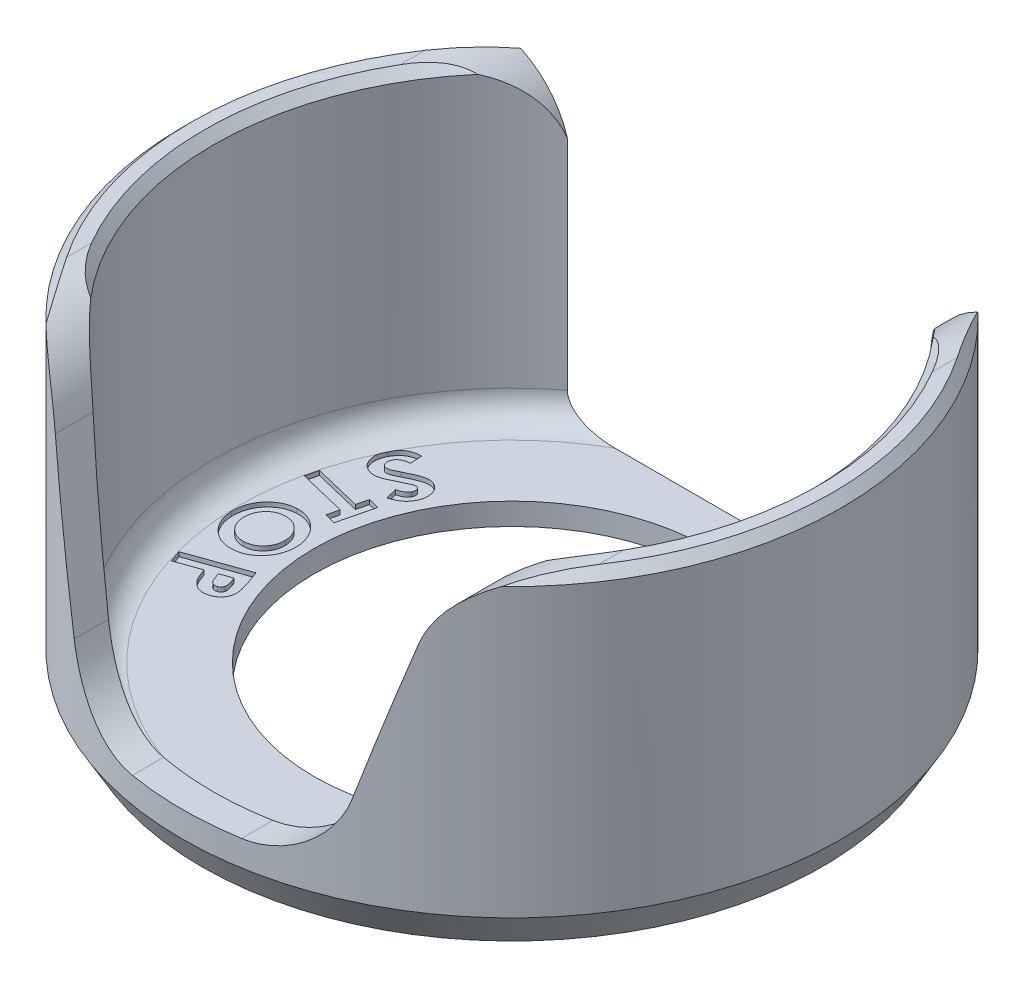
SolidWorks part; units mm, degrees
ref_plane "Front Plane" through (0, 0, 0) normal (0, 0, 1) x (1, 0, 0)
ref_plane "Top Plane" through (0, 0, 0) normal (0, 1, 0) x (1, 0, 0)
ref_plane "Right Plane" through (0, 0, 0) normal (1, 0, 0) x (0, 0, -1)
sketch "Sketch1" plane through (0, 0, 0) normal (0, 1, 0) x (1, 0, 0)
  circle A0 centre (0, 0) radius 37.5
  circle A1 centre (0, 0) radius 22.5
  dimension "D1" = 75
  dimension "D2" = 45
extrude "Boss-Extrude1" add sketch "Sketch1" along normal blind 2.5
sketch "Sketch2" plane through (0, 2.5, 0) normal (0, 1, 0) x (1, 0, 0)
  circle A0 centre (0, 0) radius 34
  circle A1 centre (0, 0) radius 37.5
extrude "Boss-Extrude2" add sketch "Sketch2" along normal blind 35
fillet "Fillet1" radius 3 1 edges at (0, 2.5, 34)
chamfer "Chamfer1" distance 1 angle 45 2 edges at (0, 37.5, 37.5) (0, 37.5, 34)
sketch "Sketch3" plane through (0, 0, 0) normal (0, 0, 1) x (1, 0, 0)
  line L8 (35, 37.5) -> (-35, 37.5) construction
  line L15 (22.8069, 37.5) -> (13.6775, 6.7652)
  line L16 (-13.6775, 6.7652) -> (-22.8069, 37.5)
  line L17 (-22.8069, 37.5) -> (22.8069, 37.5)
  line L18 (-13.6775, 6.7652) -> (13.6775, 6.7652)
  point P4 (0, 27.5)
  point P6 (0, 0)
  point P10 (0, 37.5)
  point P12 (0, 27)
  point P15 (0, 27.5)
extrude "Cut-Extrude2" cut sketch "Sketch3" against normal mid plane 109
fillet "Fillet2" radius 10 8 edges at (-22.8069, 37.5, -27.5231) (-22.8069, 37.5, 27.5231) (22.8069, 37.5, 27.5231) (22.8069, 37.5, -27.5231) (-13.6775, 6.7652, -33.0222) (13.6775, 6.7652, -33.0222) (13.6775, 6.7652, 33.0222) (-13.6775, 6.7652, 33.0222)
sketch "Sketch4" plane through (0, 2.5, 0) normal (0, 1, 0) x (1, 0, 0)
  circle A1 centre (0, 0) radius 23.4747 construction
  text T0 "<b>GENCY                                                            </b>\r\n" font "Century Gothic" height in points 26
  text T1 "<b>                           STOP</b>" font "Century Gothic" height in points 26
  text T2 "<b>                                                  EMER</b>" font "Century Gothic" height in points 26
extrude "Cut-Extrude3" cut sketch "Sketch4" against normal blind 0.5
scale "Scale1" scale about centroid uniform scaling yes scale factor 0.9
chamfer "Chamfer2" distance 2 angle 60 1 edges at (-0.0033, 1.3449, 33.7507) first distance on face at (-0.0033, 1.3449, 33.7507)
sketch "Sketch5" plane through (0, 35.0949, 0) normal (0, 1, 0) x (1, 0, 0)
  line L0 (18.6108, 24.2867) -> (-18.6174, 24.2867)
  line L2 (-18.6174, 24.2867) -> (24.6707, 24.2867)
  line L4 (-18.6096, 37.4876) -> (24.6707, 37.4876)
  line L5 (24.6707, 24.2867) -> (24.6707, 37.4876)
  line L6 (-18.6174, 24.2867) -> (-27.4898, 24.2867)
  line L8 (-18.6096, 37.4876) -> (-27.4898, 37.4876)
  line L9 (-27.4898, 24.2867) -> (-27.4898, 37.4876)
extrude "Cut-Extrude4" cut sketch "Sketch5" against normal blind 36 contours L9 L6 L0 L2 L5 L4 L8 region at (-1.4095, 35.0949, -30.8871)
